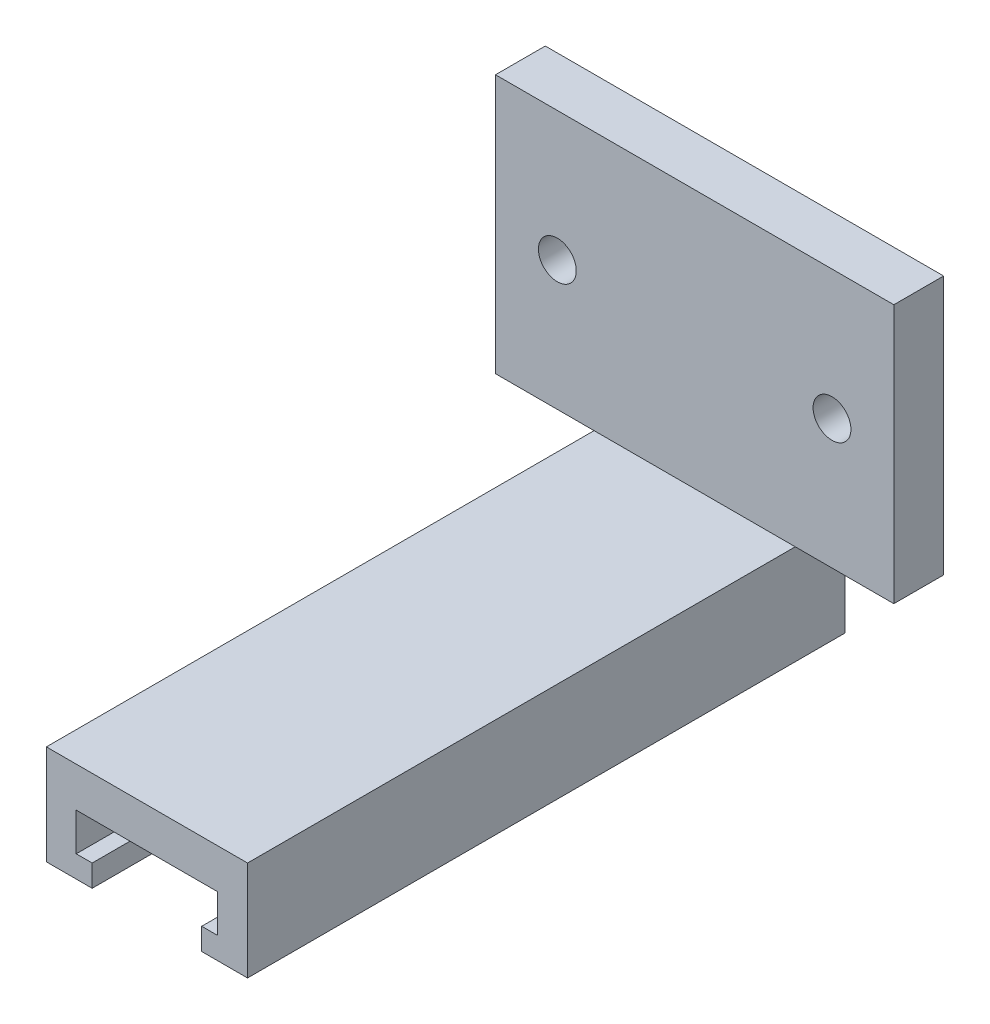
SolidWorks part; units mm, degrees
ref_plane "Front Plane" through (0, 0, 0) normal (0, 0, 1) x (1, 0, 0)
ref_plane "Top Plane" through (0, 0, 0) normal (0, 1, 0) x (1, 0, 0)
ref_plane "Right Plane" through (0, 0, 0) normal (1, 0, 0) x (0, 0, -1)
sketch "Sketch1" plane through (0, 0, 0) normal (0, 0, 1) x (1, 0, 0)
  line L0 (-12.827, 0) -> (12.827, 0)
  line L1 (12.827, 0) -> (12.827, -12.7)
  line L2 (12.827, -12.7) -> (6.985, -12.7)
  line L3 (6.985, -12.7) -> (6.985, -9.906)
  line L4 (6.985, -9.906) -> (9.017, -9.906)
  line L5 (9.017, -9.906) -> (9.017, -5.08)
  line L6 (9.017, -5.08) -> (-9.017, -5.08)
  line L7 (0, 0) -> (0, -5.08) construction
  line L8 (-9.017, -9.906) -> (-9.017, -5.08)
  line L9 (-6.985, -9.906) -> (-9.017, -9.906)
  line L10 (-6.985, -12.7) -> (-6.985, -9.906)
  line L11 (-12.827, -12.7) -> (-6.985, -12.7)
  line L12 (-12.827, 0) -> (-12.827, -12.7)
  dimension "D1" = 2.794
  dimension "D2" = 13.97
  dimension "D3" = 18.034
  dimension "D4" = 7.62
  dimension "D5" = 12.7
  dimension "D6" = 3.81
extrude "Boss-Extrude1" add sketch "Sketch1" along normal mid plane 76.2
sketch "Sketch2" plane through (0, 0, 0) normal (1, 0, 0) x (0, 0, -1)
  line L0 (-38.1, -5.08) -> (38.1, -5.08) construction
  line L1 (-38.1, -5.08) -> (38.1, -5.08) construction
  line L2 (6.858, -5.08) -> (9.398, -8.89)
  line L3 (9.398, -8.89) -> (11.938, -5.08)
  line L4 (11.938, -5.08) -> (6.858, -5.08)
  line L5 (9.398, -8.89) -> (9.398, -5.08) construction
  dimension "D1" = 3.81
  dimension "D2" = 5.08
  dimension "D3" = 47.498
extrude "Boss-Extrude2" add sketch "Sketch2" along normal mid plane 2.54 contours L3 L4 L2
sketch "Sketch3" plane through (0, 0, -38.1) normal (0, 0, -1) x (-1, 0, 0)
  line L9 (-25.4, 0) -> (25.4, 0)
  line L12 (-25.4, 0) -> (-25.4, 33.02)
  line L13 (-25.4, 33.02) -> (25.4, 33.02)
  line L17 (25.4, 0) -> (25.4, 33.02)
  line L18 (25.4, 16.51) -> (-25.4, 16.51) construction
  line L19 (-17.5133, 16.51) -> (17.5133, 16.51) construction
  circle A0 centre (17.5133, 16.51) radius 2.413
  circle A5 centre (-17.5133, 16.51) radius 2.413
  point P3 (0, 0)
  point P5 (-17.5131, 6.2754)
  point P9 (0, 41.3766)
  point P10 (-16.4271, 18.4933)
  point P12 (0, 16.51)
  dimension "D2" = 33.02
  dimension "D3" = 4.826
  dimension "D1" = 35.0266
  dimension "D4" = 50.8
extrude "Boss-Extrude3" add sketch "Sketch3" against normal blind 6.35
